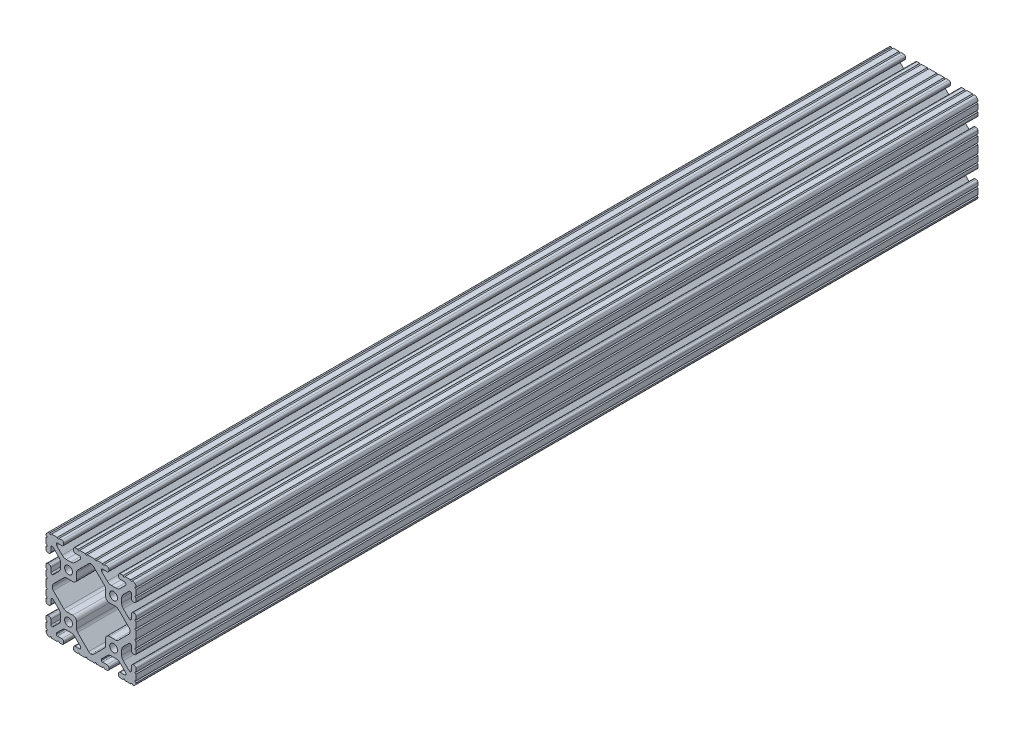
SolidWorks part; units mm, degrees
ref_plane "Front Plane" through (0, 0, 0) normal (0, 0, 1) x (1, 0, 0)
ref_plane "Top Plane" through (0, 0, 0) normal (0, 1, 0) x (1, 0, 0)
ref_plane "Right Plane" through (0, 0, 0) normal (1, 0, 0) x (0, 0, -1)
sketch "Sketch1" plane through (0, 0, 0) normal (0, 0, 1) x (1, 0, 0)
  line L0 (0, 38.1) -> (0, -38.1) construction
  line L1 (-38.1, -38.1) -> (38.1, -38.1) construction
  line L2 (-38.1, -38.1) -> (-38.1, 38.1) construction
  line L3 (-38.1, 38.1) -> (38.1, 38.1) construction
  line L4 (38.1, -38.1) -> (38.1, 38.1) construction
  line L5 (0, 38.1) -> (0, -38.1) construction
  line L6 (-38.1, 0) -> (38.1, 0) construction
  line L7 (-19.05, 19.05) -> (19.05, 19.05) construction
  line L8 (-19.05, 19.05) -> (-19.05, -19.05) construction
  line L9 (-19.05, -19.05) -> (19.05, -19.05) construction
  line L10 (19.05, 19.05) -> (19.05, -19.05) construction
  line L11 (-23.114, 38.1) -> (-23.114, -38.1) construction
  line L12 (-23.114, -38.1) -> (-14.986, 38.1) construction
  line L13 (-14.986, 38.1) -> (-14.986, -38.1) construction
  circle A0 centre (19.05, 19.05) radius 3.3274
  point P0 (0, 0)
  point P9 (0, 0)
  point P12 (-19.05, 0)
  line B0 (-11.3637, -22.8433) -> (-2.0515, -32.1555)
  line B1 (-12.2936, -15.4686) -> (-12.2936, -20.5983)
  line B2 (-20.769, -12.2936) -> (-15.4686, -12.2936)
  line B3 (-31.9021, -2.4756) -> (-23.0141, -11.3637)
  line B4 (-23.0141, 11.3637) -> (-31.9021, 2.4756)
  line B5 (-15.4686, 12.2936) -> (-20.769, 12.2936)
  line B6 (-12.2936, 20.5983) -> (-12.2936, 15.4686)
  line B7 (-2.0515, 32.1555) -> (-11.3637, 22.8433)
  line B8 (11.3637, 22.8433) -> (2.0515, 32.1555)
  line B9 (12.2936, 15.4686) -> (12.2936, 20.5983)
  line B10 (20.769, 12.2936) -> (15.4686, 12.2936)
  line B11 (31.9021, 2.4756) -> (23.0141, 11.3637)
  line B12 (23.0141, -11.3637) -> (31.9021, -2.4756)
  line B13 (15.4686, -12.2936) -> (20.769, -12.2936)
  line B14 (12.2936, -20.5983) -> (12.2936, -15.4686)
  line B15 (2.0515, -32.1555) -> (11.3637, -22.8433)
  line B16 (-4.7773, 38.1) -> (-9.6053, 38.1)
  line B17 (-11.1289, 38.1) -> (-13.4112, 38.1)
  line B18 (-14.986, 36.5252) -> (-14.986, 35.6108)
  line B19 (-13.4112, 34.036) -> (-9.652, 34.036)
  line B20 (-8.763, 33.147) -> (-8.763, 32.4935)
  line B21 (-9.0234, 31.8649) -> (-13.6907, 27.1976)
  line B22 (-17.0493, 25.8064) -> (-21.0507, 25.8064)
  line B23 (-24.4093, 27.1976) -> (-29.1002, 31.8885)
  line B24 (-29.337, 32.7207) -> (-29.337, 33.147)
  line B25 (-28.448, 34.036) -> (-24.6888, 34.036)
  line B26 (-23.114, 35.6108) -> (-23.114, 36.5252)
  line B27 (-24.6888, 38.1) -> (-27.0772, 38.1)
  line B28 (-28.6011, 38.1) -> (-33.4288, 38.1)
  line B29 (-38.1, 33.373) -> (-38.1, 28.5453)
  line B30 (-38.1, 27.0238) -> (-38.1, 24.6302)
  line B31 (-36.5252, 23.0554) -> (-35.6108, 23.0554)
  line B32 (-34.036, 24.6302) -> (-34.036, 28.448)
  line B33 (-33.147, 29.337) -> (-32.6643, 29.337)
  line B34 (-32.0357, 29.0766) -> (-27.1976, 24.2385)
  line B35 (-25.8064, 20.8799) -> (-25.8064, 17.2201)
  line B36 (-27.1976, 13.8615) -> (-31.9489, 9.1101)
  line B37 (-32.7869, 8.763) -> (-33.0603, 8.763)
  line B38 (-34.036, 9.7387) -> (-34.036, 13.4698)
  line B39 (-35.6108, 15.0446) -> (-36.5252, 15.0446)
  line B40 (-38.1, 13.4698) -> (-38.1, 11.075)
  line B41 (-38.1, 9.552) -> (-38.1, 4.7238)
  line B42 (-38.1, 3.2007) -> (-38.1, -3.2007)
  line B43 (-38.1, -4.7238) -> (-38.1, -9.552)
  line B44 (-38.1, -11.075) -> (-38.1, -13.4698)
  line B45 (-36.5252, -15.0446) -> (-35.6108, -15.0446)
  line B46 (-34.036, -13.4698) -> (-34.036, -9.7387)
  line B47 (-33.0603, -8.763) -> (-32.7869, -8.763)
  line B48 (-31.9489, -9.1101) -> (-27.1976, -13.8615)
  line B49 (-25.8064, -17.2201) -> (-25.8064, -20.8799)
  line B50 (-27.1976, -24.2385) -> (-32.0357, -29.0766)
  line B51 (-32.6643, -29.337) -> (-33.147, -29.337)
  line B52 (-34.036, -28.448) -> (-34.036, -24.6302)
  line B53 (-35.6108, -23.0554) -> (-36.5252, -23.0554)
  line B54 (-38.1, -24.6302) -> (-38.1, -27.0238)
  line B55 (-38.1, -28.5453) -> (-38.1, -33.373)
  line B56 (-33.4288, -38.1) -> (-28.6011, -38.1)
  line B57 (-27.0772, -38.1) -> (-24.6888, -38.1)
  line B58 (-23.114, -36.5252) -> (-23.114, -35.6108)
  line B59 (-24.6888, -34.036) -> (-28.448, -34.036)
  line B60 (-29.337, -33.147) -> (-29.337, -32.7207)
  line B61 (-29.1002, -31.8885) -> (-24.4093, -27.1976)
  line B62 (-21.0507, -25.8064) -> (-17.0493, -25.8064)
  line B63 (-13.6907, -27.1976) -> (-9.0234, -31.8649)
  line B64 (-8.763, -32.4935) -> (-8.763, -33.147)
  line B65 (-9.652, -34.036) -> (-13.4112, -34.036)
  line B66 (-14.986, -35.6108) -> (-14.986, -36.5252)
  line B67 (-13.4112, -38.1) -> (-11.1289, -38.1)
  line B68 (-9.6053, -38.1) -> (-4.7773, -38.1)
  line B69 (-3.2537, -38.1) -> (3.2537, -38.1)
  line B70 (4.7773, -38.1) -> (9.6053, -38.1)
  line B71 (11.1289, -38.1) -> (13.4112, -38.1)
  line B72 (14.986, -36.5252) -> (14.986, -35.6108)
  line B73 (13.4112, -34.036) -> (9.652, -34.036)
  line B74 (8.763, -33.147) -> (8.763, -32.4935)
  line B75 (9.0234, -31.8649) -> (13.6907, -27.1976)
  line B76 (17.0493, -25.8064) -> (21.0507, -25.8064)
  line B77 (24.4093, -27.1976) -> (29.1002, -31.8885)
  line B78 (29.337, -32.7207) -> (29.337, -33.147)
  line B79 (28.448, -34.036) -> (24.6888, -34.036)
  line B80 (23.114, -35.6108) -> (23.114, -36.5252)
  line B81 (24.6888, -38.1) -> (27.0772, -38.1)
  line B82 (28.6011, -38.1) -> (33.4288, -38.1)
  line B83 (38.1, -33.373) -> (38.1, -28.5453)
  line B84 (38.1, -27.0238) -> (38.1, -24.6302)
  line B85 (36.5252, -23.0554) -> (35.6108, -23.0554)
  line B86 (34.036, -24.6302) -> (34.036, -28.448)
  line B87 (33.147, -29.337) -> (32.6643, -29.337)
  line B88 (32.0357, -29.0766) -> (27.1976, -24.2385)
  line B89 (25.8064, -20.8799) -> (25.8064, -17.2201)
  line B90 (27.1976, -13.8615) -> (31.9489, -9.1101)
  line B91 (32.7869, -8.763) -> (33.0603, -8.763)
  line B92 (34.036, -9.7387) -> (34.036, -13.4698)
  line B93 (35.6108, -15.0446) -> (36.5252, -15.0446)
  line B94 (38.1, -13.4698) -> (38.1, -11.075)
  line B95 (38.1, -9.552) -> (38.1, -4.7238)
  line B96 (38.1, -3.2007) -> (38.1, 3.2007)
  line B97 (38.1, 4.7238) -> (38.1, 9.552)
  line B98 (38.1, 11.075) -> (38.1, 13.4698)
  line B99 (36.5252, 15.0446) -> (35.6108, 15.0446)
  line B100 (34.036, 13.4698) -> (34.036, 9.7387)
  line B101 (33.0603, 8.763) -> (32.7869, 8.763)
  line B102 (31.9489, 9.1101) -> (27.1976, 13.8615)
  line B103 (25.8064, 17.2201) -> (25.8064, 20.8799)
  line B104 (27.1976, 24.2385) -> (32.0357, 29.0766)
  line B105 (32.6643, 29.337) -> (33.147, 29.337)
  line B106 (34.036, 28.448) -> (34.036, 24.6302)
  line B107 (35.6108, 23.0554) -> (36.5252, 23.0554)
  line B108 (38.1, 24.6302) -> (38.1, 27.0238)
  line B109 (38.1, 28.5453) -> (38.1, 33.373)
  line B110 (33.4288, 38.1) -> (28.6011, 38.1)
  line B111 (27.0772, 38.1) -> (24.6888, 38.1)
  line B112 (23.114, 36.5252) -> (23.114, 35.6108)
  line B113 (24.6888, 34.036) -> (28.448, 34.036)
  line B114 (29.337, 33.147) -> (29.337, 32.7207)
  line B115 (29.1002, 31.8885) -> (24.4093, 27.1976)
  line B116 (21.0507, 25.8064) -> (17.0493, 25.8064)
  line B117 (13.6907, 27.1976) -> (9.0234, 31.8649)
  line B118 (8.763, 32.4935) -> (8.763, 33.147)
  line B119 (9.652, 34.036) -> (13.4112, 34.036)
  line B120 (14.986, 35.6108) -> (14.986, 36.5252)
  line B121 (13.4112, 38.1) -> (11.1289, 38.1)
  line B122 (9.6053, 38.1) -> (4.7773, 38.1)
  line B123 (3.2537, 38.1) -> (-3.2537, 38.1)
  circle B124 centre (-19.05, 19.05) radius 3.3274
  circle B125 centre (-19.05, -19.05) radius 3.3274
  circle B126 centre (19.05, -19.05) radius 3.3274
  circle B127 centre (19.05, 19.05) radius 3.3274
  arc B128 (0, -33.011) -> (2.0515, -32.1555) centre (-0.0139, -30.09) ccw
  arc B129 (-2.0515, -32.1555) -> (0, -33.011) centre (0.0139, -30.09) ccw
  arc B130 (-12.2936, -20.5983) -> (-11.3637, -22.8433) centre (-9.1186, -20.5983) ccw
  arc B131 (-12.2936, -15.4686) -> (-15.4686, -12.2936) centre (-15.4686, -15.4686) ccw
  arc B132 (-23.0141, -11.3637) -> (-20.769, -12.2936) centre (-20.769, -9.1186) ccw
  arc B133 (-32.7287, 0) -> (-31.9021, -2.4756) centre (-29.8367, -0.4102) ccw
  arc B134 (-31.9021, 2.4756) -> (-32.7287, 0) centre (-29.8367, 0.4102) ccw
  arc B135 (-20.769, 12.2936) -> (-23.0141, 11.3637) centre (-20.769, 9.1186) ccw
  arc B136 (-15.4686, 12.2936) -> (-12.2936, 15.4686) centre (-15.4686, 15.4686) ccw
  arc B137 (-11.3637, 22.8433) -> (-12.2936, 20.5983) centre (-9.1186, 20.5983) ccw
  arc B138 (0, 33.011) -> (-2.0515, 32.1555) centre (0.0139, 30.09) ccw
  arc B139 (2.0515, 32.1555) -> (0, 33.011) centre (-0.0139, 30.09) ccw
  arc B140 (12.2936, 20.5983) -> (11.3637, 22.8433) centre (9.1186, 20.5983) ccw
  arc B141 (12.2936, 15.4686) -> (15.4686, 12.2936) centre (15.4686, 15.4686) ccw
  arc B142 (23.0141, 11.3637) -> (20.769, 12.2936) centre (20.769, 9.1186) ccw
  arc B143 (32.7287, 0) -> (31.9021, 2.4756) centre (29.8367, 0.4102) ccw
  arc B144 (31.9021, -2.4756) -> (32.7287, 0) centre (29.8367, -0.4102) ccw
  arc B145 (20.769, -12.2936) -> (23.0141, -11.3637) centre (20.769, -9.1186) ccw
  arc B146 (15.4686, -12.2936) -> (12.2936, -15.4686) centre (15.4686, -15.4686) ccw
  arc B147 (11.3637, -22.8433) -> (12.2936, -20.5983) centre (9.1186, -20.5983) ccw
  arc B148 (-4.7773, 38.1) -> (-3.2537, 38.1) centre (-4.0155, 38.0824) ccw
  arc B149 (-11.1289, 38.1) -> (-9.6053, 38.1) centre (-10.3671, 38.0824) ccw
  arc B150 (-13.4112, 38.1) -> (-14.986, 36.5252) centre (-13.4112, 36.5252) ccw
  arc B151 (-14.986, 35.6108) -> (-13.4112, 34.036) centre (-13.4112, 35.6108) ccw
  arc B152 (-8.763, 33.147) -> (-9.652, 34.036) centre (-9.652, 33.147) ccw
  arc B153 (-9.0234, 31.8649) -> (-8.763, 32.4935) centre (-9.652, 32.4935) ccw
  arc B154 (-17.0493, 25.8064) -> (-13.6907, 27.1976) centre (-17.0493, 30.5562) ccw
  arc B155 (-24.4093, 27.1976) -> (-21.0507, 25.8064) centre (-21.0507, 30.5562) ccw
  arc B156 (-29.337, 32.7207) -> (-29.1002, 31.8885) centre (-28.4716, 32.5172) ccw
  arc B157 (-28.448, 34.036) -> (-29.337, 33.147) centre (-28.448, 33.147) ccw
  arc B158 (-24.6888, 34.036) -> (-23.114, 35.6108) centre (-24.6888, 35.6108) ccw
  arc B159 (-23.114, 36.5252) -> (-24.6888, 38.1) centre (-24.6888, 36.5252) ccw
  arc B160 (-28.6011, 38.1) -> (-27.0772, 38.1) centre (-27.8392, 38.0824) ccw
  arc B161 (-34.9527, 38.1) -> (-33.4288, 38.1) centre (-34.1907, 38.0824) ccw
  arc B162 (-34.9527, 38.1) -> (-37.0861, 37.1826) centre (-34.8521, 34.9266) ccw
  arc B163 (-37.0861, 37.1826) -> (-38.1, 34.8455) centre (-34.925, 34.8566) ccw
  arc B164 (-38.1, 33.373) -> (-38.1, 34.8455) centre (-37.9035, 34.1092) ccw
  arc B165 (-38.1, 27.0238) -> (-38.1, 28.5453) centre (-37.9035, 27.7845) ccw
  arc B166 (-38.1, 24.6302) -> (-36.5252, 23.0554) centre (-36.5252, 24.6302) ccw
  arc B167 (-35.6108, 23.0554) -> (-34.036, 24.6302) centre (-35.6108, 24.6302) ccw
  arc B168 (-33.147, 29.337) -> (-34.036, 28.448) centre (-33.147, 28.448) ccw
  arc B169 (-32.0357, 29.0766) -> (-32.6643, 29.337) centre (-32.6643, 28.448) ccw
  arc B170 (-25.8064, 20.8799) -> (-27.1976, 24.2385) centre (-30.5562, 20.8799) ccw
  arc B171 (-27.1976, 13.8615) -> (-25.8064, 17.2201) centre (-30.5562, 17.2201) ccw
  arc B172 (-32.7869, 8.763) -> (-31.9489, 9.1101) centre (-32.7869, 9.9481) ccw
  arc B173 (-34.036, 9.7387) -> (-33.0603, 8.763) centre (-33.0603, 9.7387) ccw
  arc B174 (-34.036, 13.4698) -> (-35.6108, 15.0446) centre (-35.6108, 13.4698) ccw
  arc B175 (-36.5252, 15.0446) -> (-38.1, 13.4698) centre (-36.5252, 13.4698) ccw
  arc B176 (-38.1, 9.552) -> (-38.1, 11.075) centre (-37.9035, 10.3135) ccw
  arc B177 (-38.1, 3.2007) -> (-38.1, 4.7238) centre (-37.9035, 3.9622) ccw
  arc B178 (-38.1, -4.7238) -> (-38.1, -3.2007) centre (-37.9035, -3.9622) ccw
  arc B179 (-38.1, -11.075) -> (-38.1, -9.552) centre (-37.9035, -10.3135) ccw
  arc B180 (-38.1, -13.4698) -> (-36.5252, -15.0446) centre (-36.5252, -13.4698) ccw
  arc B181 (-35.6108, -15.0446) -> (-34.036, -13.4698) centre (-35.6108, -13.4698) ccw
  arc B182 (-33.0603, -8.763) -> (-34.036, -9.7387) centre (-33.0603, -9.7387) ccw
  arc B183 (-31.9489, -9.1101) -> (-32.7869, -8.763) centre (-32.7869, -9.9481) ccw
  arc B184 (-25.8064, -17.2201) -> (-27.1976, -13.8615) centre (-30.5562, -17.2201) ccw
  arc B185 (-27.1976, -24.2385) -> (-25.8064, -20.8799) centre (-30.5562, -20.8799) ccw
  arc B186 (-32.6643, -29.337) -> (-32.0357, -29.0766) centre (-32.6643, -28.448) ccw
  arc B187 (-34.036, -28.448) -> (-33.147, -29.337) centre (-33.147, -28.448) ccw
  arc B188 (-34.036, -24.6302) -> (-35.6108, -23.0554) centre (-35.6108, -24.6302) ccw
  arc B189 (-36.5252, -23.0554) -> (-38.1, -24.6302) centre (-36.5252, -24.6302) ccw
  arc B190 (-38.1, -28.5453) -> (-38.1, -27.0238) centre (-37.9035, -27.7845) ccw
  arc B191 (-38.1, -34.8455) -> (-38.1, -33.373) centre (-37.9035, -34.1092) ccw
  arc B192 (-38.1, -34.8455) -> (-37.0861, -37.1826) centre (-34.925, -34.8566) ccw
  arc B193 (-37.0861, -37.1826) -> (-34.9527, -38.1) centre (-34.8521, -34.9266) ccw
  arc B194 (-33.4288, -38.1) -> (-34.9527, -38.1) centre (-34.1907, -38.0824) ccw
  arc B195 (-27.0772, -38.1) -> (-28.6011, -38.1) centre (-27.8392, -38.0824) ccw
  arc B196 (-24.6888, -38.1) -> (-23.114, -36.5252) centre (-24.6888, -36.5252) ccw
  arc B197 (-23.114, -35.6108) -> (-24.6888, -34.036) centre (-24.6888, -35.6108) ccw
  arc B198 (-29.337, -33.147) -> (-28.448, -34.036) centre (-28.448, -33.147) ccw
  arc B199 (-29.1002, -31.8885) -> (-29.337, -32.7207) centre (-28.4716, -32.5172) ccw
  arc B200 (-21.0507, -25.8064) -> (-24.4093, -27.1976) centre (-21.0507, -30.5562) ccw
  arc B201 (-13.6907, -27.1976) -> (-17.0493, -25.8064) centre (-17.0493, -30.5562) ccw
  arc B202 (-8.763, -32.4935) -> (-9.0234, -31.8649) centre (-9.652, -32.4935) ccw
  arc B203 (-9.652, -34.036) -> (-8.763, -33.147) centre (-9.652, -33.147) ccw
  arc B204 (-13.4112, -34.036) -> (-14.986, -35.6108) centre (-13.4112, -35.6108) ccw
  arc B205 (-14.986, -36.5252) -> (-13.4112, -38.1) centre (-13.4112, -36.5252) ccw
  arc B206 (-9.6053, -38.1) -> (-11.1289, -38.1) centre (-10.3671, -38.0824) ccw
  arc B207 (-3.2537, -38.1) -> (-4.7773, -38.1) centre (-4.0155, -38.0824) ccw
  arc B208 (4.7773, -38.1) -> (3.2537, -38.1) centre (4.0155, -38.0824) ccw
  arc B209 (11.1289, -38.1) -> (9.6053, -38.1) centre (10.3671, -38.0824) ccw
  arc B210 (13.4112, -38.1) -> (14.986, -36.5252) centre (13.4112, -36.5252) ccw
  arc B211 (14.986, -35.6108) -> (13.4112, -34.036) centre (13.4112, -35.6108) ccw
  arc B212 (8.763, -33.147) -> (9.652, -34.036) centre (9.652, -33.147) ccw
  arc B213 (9.0234, -31.8649) -> (8.763, -32.4935) centre (9.652, -32.4935) ccw
  arc B214 (17.0493, -25.8064) -> (13.6907, -27.1976) centre (17.0493, -30.5562) ccw
  arc B215 (24.4093, -27.1976) -> (21.0507, -25.8064) centre (21.0507, -30.5562) ccw
  arc B216 (29.337, -32.7207) -> (29.1002, -31.8885) centre (28.4716, -32.5172) ccw
  arc B217 (28.448, -34.036) -> (29.337, -33.147) centre (28.448, -33.147) ccw
  arc B218 (24.6888, -34.036) -> (23.114, -35.6108) centre (24.6888, -35.6108) ccw
  arc B219 (23.114, -36.5252) -> (24.6888, -38.1) centre (24.6888, -36.5252) ccw
  arc B220 (28.6011, -38.1) -> (27.0772, -38.1) centre (27.8392, -38.0824) ccw
  arc B221 (34.9527, -38.1) -> (33.4288, -38.1) centre (34.1907, -38.0824) ccw
  arc B222 (34.9527, -38.1) -> (37.0861, -37.1826) centre (34.8521, -34.9266) ccw
  arc B223 (37.0861, -37.1826) -> (38.1, -34.8455) centre (34.925, -34.8566) ccw
  arc B224 (38.1, -33.373) -> (38.1, -34.8455) centre (37.9035, -34.1092) ccw
  arc B225 (38.1, -27.0238) -> (38.1, -28.5453) centre (37.9035, -27.7845) ccw
  arc B226 (38.1, -24.6302) -> (36.5252, -23.0554) centre (36.5252, -24.6302) ccw
  arc B227 (35.6108, -23.0554) -> (34.036, -24.6302) centre (35.6108, -24.6302) ccw
  arc B228 (33.147, -29.337) -> (34.036, -28.448) centre (33.147, -28.448) ccw
  arc B229 (32.0357, -29.0766) -> (32.6643, -29.337) centre (32.6643, -28.448) ccw
  arc B230 (25.8064, -20.8799) -> (27.1976, -24.2385) centre (30.5562, -20.8799) ccw
  arc B231 (27.1976, -13.8615) -> (25.8064, -17.2201) centre (30.5562, -17.2201) ccw
  arc B232 (32.7869, -8.763) -> (31.9489, -9.1101) centre (32.7869, -9.9481) ccw
  arc B233 (34.036, -9.7387) -> (33.0603, -8.763) centre (33.0603, -9.7387) ccw
  arc B234 (34.036, -13.4698) -> (35.6108, -15.0446) centre (35.6108, -13.4698) ccw
  arc B235 (36.5252, -15.0446) -> (38.1, -13.4698) centre (36.5252, -13.4698) ccw
  arc B236 (38.1, -9.552) -> (38.1, -11.075) centre (37.9035, -10.3135) ccw
  arc B237 (38.1, -3.2007) -> (38.1, -4.7238) centre (37.9035, -3.9622) ccw
  arc B238 (38.1, 4.7238) -> (38.1, 3.2007) centre (37.9035, 3.9622) ccw
  arc B239 (38.1, 11.075) -> (38.1, 9.552) centre (37.9035, 10.3135) ccw
  arc B240 (38.1, 13.4698) -> (36.5252, 15.0446) centre (36.5252, 13.4698) ccw
  arc B241 (35.6108, 15.0446) -> (34.036, 13.4698) centre (35.6108, 13.4698) ccw
  arc B242 (33.0603, 8.763) -> (34.036, 9.7387) centre (33.0603, 9.7387) ccw
  arc B243 (31.9489, 9.1101) -> (32.7869, 8.763) centre (32.7869, 9.9481) ccw
  arc B244 (25.8064, 17.2201) -> (27.1976, 13.8615) centre (30.5562, 17.2201) ccw
  arc B245 (27.1976, 24.2385) -> (25.8064, 20.8799) centre (30.5562, 20.8799) ccw
  arc B246 (32.6643, 29.337) -> (32.0357, 29.0766) centre (32.6643, 28.448) ccw
  arc B247 (34.036, 28.448) -> (33.147, 29.337) centre (33.147, 28.448) ccw
  arc B248 (34.036, 24.6302) -> (35.6108, 23.0554) centre (35.6108, 24.6302) ccw
  arc B249 (36.5252, 23.0554) -> (38.1, 24.6302) centre (36.5252, 24.6302) ccw
  arc B250 (38.1, 28.5453) -> (38.1, 27.0238) centre (37.9035, 27.7845) ccw
  arc B251 (38.1, 34.8455) -> (38.1, 33.373) centre (37.9035, 34.1092) ccw
  arc B252 (38.1, 34.8455) -> (37.0861, 37.1826) centre (34.925, 34.8566) ccw
  arc B253 (37.0861, 37.1826) -> (34.9527, 38.1) centre (34.8521, 34.9266) ccw
  arc B254 (33.4288, 38.1) -> (34.9527, 38.1) centre (34.1907, 38.0824) ccw
  arc B255 (27.0772, 38.1) -> (28.6011, 38.1) centre (27.8392, 38.0824) ccw
  arc B256 (24.6888, 38.1) -> (23.114, 36.5252) centre (24.6888, 36.5252) ccw
  arc B257 (23.114, 35.6108) -> (24.6888, 34.036) centre (24.6888, 35.6108) ccw
  arc B258 (29.337, 33.147) -> (28.448, 34.036) centre (28.448, 33.147) ccw
  arc B259 (29.1002, 31.8885) -> (29.337, 32.7207) centre (28.4716, 32.5172) ccw
  arc B260 (21.0507, 25.8064) -> (24.4093, 27.1976) centre (21.0507, 30.5562) ccw
  arc B261 (13.6907, 27.1976) -> (17.0493, 25.8064) centre (17.0493, 30.5562) ccw
  arc B262 (8.763, 32.4935) -> (9.0234, 31.8649) centre (9.652, 32.4935) ccw
  arc B263 (9.652, 34.036) -> (8.763, 33.147) centre (9.652, 33.147) ccw
  arc B264 (13.4112, 34.036) -> (14.986, 35.6108) centre (13.4112, 35.6108) ccw
  arc B265 (14.986, 36.5252) -> (13.4112, 38.1) centre (13.4112, 36.5252) ccw
  arc B266 (9.6053, 38.1) -> (11.1289, 38.1) centre (10.3671, 38.0824) ccw
  arc B267 (3.2537, 38.1) -> (4.7773, 38.1) centre (4.0155, 38.0824) ccw
  dimension "Center Hole Diameter" = 6.6548
  dimension "Rail Width" = 76.2
  dimension "Rail Height" = 76.2
  dimension "T-Slot Width" = 8.128
sketch_block_instance "Block1-1"
sketch_block "Block1"
sketch "Sketch2" plane through (0, 0, 0) normal (1, 0, 0) x (0, 0, -1)
  line L0 (-355.6, 0) -> (355.6, 0) construction
  line L1 (-355.6, 38.1) -> (-355.6, -38.1) construction
  line L2 (-355.6, -38.1) -> (355.6, -38.1) construction
  line L3 (355.6, -38.1) -> (355.6, 38.1) construction
  line L4 (-254, 0) -> (-254, 38.1) construction
  line L5 (-254, 38.1) -> (254, 38.1) construction
  line L6 (254, 38.1) -> (254, 0) construction
  point P5 (254, 0)
  point P10 (-254, 0)
  dimension "D1" = 101.6
  dimension "Length" = 711.2
  dimension "D2" = 101.6
sketch "Sketch3" plane through (0, 0, 0) normal (0, 0, 1) x (1, 0, 0)
  line L0 (-11.3637, -22.8433) -> (-2.0515, -32.1555) construction
  line L1 (-12.2936, -15.4686) -> (-12.2936, -20.5983) construction
  line L2 (-20.769, -12.2936) -> (-15.4686, -12.2936) construction
  line L3 (-31.9021, -2.4756) -> (-23.0141, -11.3637) construction
  line L4 (-23.0141, 11.3637) -> (-31.9021, 2.4756) construction
  line L5 (-15.4686, 12.2936) -> (-20.769, 12.2936) construction
  line L6 (-12.2936, 20.5983) -> (-12.2936, 15.4686) construction
  line L7 (-2.0515, 32.1555) -> (-11.3637, 22.8433) construction
  line L8 (11.3637, 22.8433) -> (2.0515, 32.1555) construction
  line L9 (12.2936, 15.4686) -> (12.2936, 20.5983) construction
  line L10 (20.769, 12.2936) -> (15.4686, 12.2936) construction
  line L11 (31.9021, 2.4756) -> (23.0141, 11.3637) construction
  line L12 (23.0141, -11.3637) -> (31.9021, -2.4756) construction
  line L13 (15.4686, -12.2936) -> (20.769, -12.2936) construction
  line L14 (12.2936, -20.5983) -> (12.2936, -15.4686) construction
  line L15 (2.0515, -32.1555) -> (11.3637, -22.8433) construction
  line L16 (34.036, 28.448) -> (34.036, 24.6302) construction
  line L17 (35.6108, 23.0554) -> (36.5252, 23.0554) construction
  line L18 (38.1, 24.6302) -> (38.1, 27.0238) construction
  line L19 (38.1, 28.5453) -> (38.1, 33.373) construction
  line L20 (33.4288, 38.1) -> (28.6011, 38.1) construction
  line L21 (27.0772, 38.1) -> (24.6888, 38.1) construction
  line L22 (23.114, 36.5252) -> (23.114, 35.6108) construction
  line L23 (24.6888, 34.036) -> (28.448, 34.036) construction
  line L24 (29.337, 33.147) -> (29.337, 32.7207) construction
  line L25 (29.1002, 31.8885) -> (24.4093, 27.1976) construction
  line L26 (21.0507, 25.8064) -> (17.0493, 25.8064) construction
  line L27 (13.6907, 27.1976) -> (9.0234, 31.8649) construction
  line L28 (8.763, 32.4935) -> (8.763, 33.147) construction
  line L29 (9.652, 34.036) -> (13.4112, 34.036) construction
  line L30 (14.986, 35.6108) -> (14.986, 36.5252) construction
  line L31 (13.4112, 38.1) -> (11.1289, 38.1) construction
  line L32 (9.6053, 38.1) -> (4.7773, 38.1) construction
  line L33 (3.2537, 38.1) -> (-3.2537, 38.1) construction
  line L34 (-4.7773, 38.1) -> (-9.6053, 38.1) construction
  line L35 (-11.1289, 38.1) -> (-13.4112, 38.1) construction
  line L36 (-14.986, 36.5252) -> (-14.986, 35.6108) construction
  line L37 (-13.4112, 34.036) -> (-9.652, 34.036) construction
  line L38 (-8.763, 33.147) -> (-8.763, 32.4935) construction
  line L39 (-9.0234, 31.8649) -> (-13.6907, 27.1976) construction
  line L40 (-17.0493, 25.8064) -> (-21.0507, 25.8064) construction
  line L41 (-24.4093, 27.1976) -> (-29.1002, 31.8885) construction
  line L42 (-29.337, 32.7207) -> (-29.337, 33.147) construction
  line L43 (-28.448, 34.036) -> (-24.6888, 34.036) construction
  line L44 (-23.114, 35.6108) -> (-23.114, 36.5252) construction
  line L45 (-24.6888, 38.1) -> (-27.0772, 38.1) construction
  line L46 (-28.6011, 38.1) -> (-33.4288, 38.1) construction
  line L47 (-38.1, 33.373) -> (-38.1, 28.5453) construction
  line L48 (-38.1, 27.0238) -> (-38.1, 24.6302) construction
  line L49 (-36.5252, 23.0554) -> (-35.6108, 23.0554) construction
  line L50 (-34.036, 24.6302) -> (-34.036, 28.448) construction
  line L51 (-33.147, 29.337) -> (-32.6643, 29.337) construction
  line L52 (-32.0357, 29.0766) -> (-27.1976, 24.2385) construction
  line L53 (-25.8064, 20.8799) -> (-25.8064, 17.2201) construction
  line L54 (-27.1976, 13.8615) -> (-31.9489, 9.1101) construction
  line L55 (-32.7869, 8.763) -> (-33.0603, 8.763) construction
  line L56 (-34.036, 9.7387) -> (-34.036, 13.4698) construction
  line L57 (-35.6108, 15.0446) -> (-36.5252, 15.0446) construction
  line L58 (-38.1, 13.4698) -> (-38.1, 11.075) construction
  line L59 (-38.1, 9.552) -> (-38.1, 4.7238) construction
  line L60 (-38.1, 3.2007) -> (-38.1, -3.2007) construction
  line L61 (-38.1, -4.7238) -> (-38.1, -9.552) construction
  line L62 (-38.1, -11.075) -> (-38.1, -13.4698) construction
  line L63 (-36.5252, -15.0446) -> (-35.6108, -15.0446) construction
  line L64 (-34.036, -13.4698) -> (-34.036, -9.7387) construction
  line L65 (-33.0603, -8.763) -> (-32.7869, -8.763) construction
  line L66 (-31.9489, -9.1101) -> (-27.1976, -13.8615) construction
  line L67 (-25.8064, -17.2201) -> (-25.8064, -20.8799) construction
  line L68 (-27.1976, -24.2385) -> (-32.0357, -29.0766) construction
  line L69 (-32.6643, -29.337) -> (-33.147, -29.337) construction
  line L70 (-34.036, -28.448) -> (-34.036, -24.6302) construction
  line L71 (-35.6108, -23.0554) -> (-36.5252, -23.0554) construction
  line L72 (-38.1, -24.6302) -> (-38.1, -27.0238) construction
  line L73 (-38.1, -28.5453) -> (-38.1, -33.373) construction
  line L74 (-33.4288, -38.1) -> (-28.6011, -38.1) construction
  line L75 (-27.0772, -38.1) -> (-24.6888, -38.1) construction
  line L76 (-23.114, -36.5252) -> (-23.114, -35.6108) construction
  line L77 (-24.6888, -34.036) -> (-28.448, -34.036) construction
  line L78 (-29.337, -33.147) -> (-29.337, -32.7207) construction
  line L79 (-29.1002, -31.8885) -> (-24.4093, -27.1976) construction
  line L80 (-21.0507, -25.8064) -> (-17.0493, -25.8064) construction
  line L81 (-13.6907, -27.1976) -> (-9.0234, -31.8649) construction
  line L82 (-8.763, -32.4935) -> (-8.763, -33.147) construction
  line L83 (-9.652, -34.036) -> (-13.4112, -34.036) construction
  line L84 (-14.986, -35.6108) -> (-14.986, -36.5252) construction
  line L85 (-13.4112, -38.1) -> (-11.1289, -38.1) construction
  line L86 (-9.6053, -38.1) -> (-4.7773, -38.1) construction
  line L87 (-3.2537, -38.1) -> (3.2537, -38.1) construction
  line L88 (4.7773, -38.1) -> (9.6053, -38.1) construction
  line L89 (11.1289, -38.1) -> (13.4112, -38.1) construction
  line L90 (14.986, -36.5252) -> (14.986, -35.6108) construction
  line L91 (13.4112, -34.036) -> (9.652, -34.036) construction
  line L92 (8.763, -33.147) -> (8.763, -32.4935) construction
  line L93 (9.0234, -31.8649) -> (13.6907, -27.1976) construction
  line L94 (17.0493, -25.8064) -> (21.0507, -25.8064) construction
  line L95 (24.4093, -27.1976) -> (29.1002, -31.8885) construction
  line L96 (29.337, -32.7207) -> (29.337, -33.147) construction
  line L97 (28.448, -34.036) -> (24.6888, -34.036) construction
  line L98 (23.114, -35.6108) -> (23.114, -36.5252) construction
  line L99 (24.6888, -38.1) -> (27.0772, -38.1) construction
  line L100 (28.6011, -38.1) -> (33.4288, -38.1) construction
  line L101 (38.1, -33.373) -> (38.1, -28.5453) construction
  line L102 (38.1, -27.0238) -> (38.1, -24.6302) construction
  line L103 (36.5252, -23.0554) -> (35.6108, -23.0554) construction
  line L104 (34.036, -24.6302) -> (34.036, -28.448) construction
  line L105 (33.147, -29.337) -> (32.6643, -29.337) construction
  line L106 (32.0357, -29.0766) -> (27.1976, -24.2385) construction
  line L107 (25.8064, -20.8799) -> (25.8064, -17.2201) construction
  line L108 (27.1976, -13.8615) -> (31.9489, -9.1101) construction
  line L109 (32.7869, -8.763) -> (33.0603, -8.763) construction
  line L110 (34.036, -9.7387) -> (34.036, -13.4698) construction
  line L111 (35.6108, -15.0446) -> (36.5252, -15.0446) construction
  line L112 (38.1, -13.4698) -> (38.1, -11.075) construction
  line L113 (38.1, -9.552) -> (38.1, -4.7238) construction
  line L114 (38.1, -3.2007) -> (38.1, 3.2007) construction
  line L115 (38.1, 4.7238) -> (38.1, 9.552) construction
  line L116 (38.1, 11.075) -> (38.1, 13.4698) construction
  line L117 (36.5252, 15.0446) -> (35.6108, 15.0446) construction
  line L118 (34.036, 13.4698) -> (34.036, 9.7387) construction
  line L119 (33.0603, 8.763) -> (32.7869, 8.763) construction
  line L120 (31.9489, 9.1101) -> (27.1976, 13.8615) construction
  line L121 (25.8064, 17.2201) -> (25.8064, 20.8799) construction
  line L122 (27.1976, 24.2385) -> (32.0357, 29.0766) construction
  line L123 (32.6643, 29.337) -> (33.147, 29.337) construction
  line L124 (-11.3637, -22.8433) -> (-2.0515, -32.1555)
  line L125 (-12.2936, -15.4686) -> (-12.2936, -20.5983)
  line L126 (-20.769, -12.2936) -> (-15.4686, -12.2936)
  line L127 (-31.9021, -2.4756) -> (-23.0141, -11.3637)
  line L128 (-23.0141, 11.3637) -> (-31.9021, 2.4756)
  line L129 (-15.4686, 12.2936) -> (-20.769, 12.2936)
  line L130 (-12.2936, 20.5983) -> (-12.2936, 15.4686)
  line L131 (-2.0515, 32.1555) -> (-11.3637, 22.8433)
  line L132 (11.3637, 22.8433) -> (2.0515, 32.1555)
  line L133 (12.2936, 15.4686) -> (12.2936, 20.5983)
  line L134 (20.769, 12.2936) -> (15.4686, 12.2936)
  line L135 (31.9021, 2.4756) -> (23.0141, 11.3637)
  line L136 (23.0141, -11.3637) -> (31.9021, -2.4756)
  line L137 (15.4686, -12.2936) -> (20.769, -12.2936)
  line L138 (12.2936, -20.5983) -> (12.2936, -15.4686)
  line L139 (2.0515, -32.1555) -> (11.3637, -22.8433)
  line L140 (34.036, 28.448) -> (34.036, 24.6302)
  line L141 (35.6108, 23.0554) -> (36.5252, 23.0554)
  line L142 (38.1, 24.6302) -> (38.1, 27.0238)
  line L143 (38.1, 28.5453) -> (38.1, 33.373)
  line L144 (33.4288, 38.1) -> (28.6011, 38.1)
  line L145 (27.0772, 38.1) -> (24.6888, 38.1)
  line L146 (23.114, 36.5252) -> (23.114, 35.6108)
  line L147 (24.6888, 34.036) -> (28.448, 34.036)
  line L148 (29.337, 33.147) -> (29.337, 32.7207)
  line L149 (29.1002, 31.8885) -> (24.4093, 27.1976)
  line L150 (21.0507, 25.8064) -> (17.0493, 25.8064)
  line L151 (13.6907, 27.1976) -> (9.0234, 31.8649)
  line L152 (8.763, 32.4935) -> (8.763, 33.147)
  line L153 (9.652, 34.036) -> (13.4112, 34.036)
  line L154 (14.986, 35.6108) -> (14.986, 36.5252)
  line L155 (13.4112, 38.1) -> (11.1289, 38.1)
  line L156 (9.6053, 38.1) -> (4.7773, 38.1)
  line L157 (3.2537, 38.1) -> (-3.2537, 38.1)
  line L158 (-4.7773, 38.1) -> (-9.6053, 38.1)
  line L159 (-11.1289, 38.1) -> (-13.4112, 38.1)
  line L160 (-14.986, 36.5252) -> (-14.986, 35.6108)
  line L161 (-13.4112, 34.036) -> (-9.652, 34.036)
  line L162 (-8.763, 33.147) -> (-8.763, 32.4935)
  line L163 (-9.0234, 31.8649) -> (-13.6907, 27.1976)
  line L164 (-17.0493, 25.8064) -> (-21.0507, 25.8064)
  line L165 (-24.4093, 27.1976) -> (-29.1002, 31.8885)
  line L166 (-29.337, 32.7207) -> (-29.337, 33.147)
  line L167 (-28.448, 34.036) -> (-24.6888, 34.036)
  line L168 (-23.114, 35.6108) -> (-23.114, 36.5252)
  line L169 (-24.6888, 38.1) -> (-27.0772, 38.1)
  line L170 (-28.6011, 38.1) -> (-33.4288, 38.1)
  line L171 (-38.1, 33.373) -> (-38.1, 28.5453)
  line L172 (-38.1, 27.0238) -> (-38.1, 24.6302)
  line L173 (-36.5252, 23.0554) -> (-35.6108, 23.0554)
  line L174 (-34.036, 24.6302) -> (-34.036, 28.448)
  line L175 (-33.147, 29.337) -> (-32.6643, 29.337)
  line L176 (-32.0357, 29.0766) -> (-27.1976, 24.2385)
  line L177 (-25.8064, 20.8799) -> (-25.8064, 17.2201)
  line L178 (-27.1976, 13.8615) -> (-31.9489, 9.1101)
  line L179 (-32.7869, 8.763) -> (-33.0603, 8.763)
  line L180 (-34.036, 9.7387) -> (-34.036, 13.4698)
  line L181 (-35.6108, 15.0446) -> (-36.5252, 15.0446)
  line L182 (-38.1, 13.4698) -> (-38.1, 11.075)
  line L183 (-38.1, 9.552) -> (-38.1, 4.7238)
  line L184 (-38.1, 3.2007) -> (-38.1, -3.2007)
  line L185 (-38.1, -4.7238) -> (-38.1, -9.552)
  line L186 (-38.1, -11.075) -> (-38.1, -13.4698)
  line L187 (-36.5252, -15.0446) -> (-35.6108, -15.0446)
  line L188 (-34.036, -13.4698) -> (-34.036, -9.7387)
  line L189 (-33.0603, -8.763) -> (-32.7869, -8.763)
  line L190 (-31.9489, -9.1101) -> (-27.1976, -13.8615)
  line L191 (-25.8064, -17.2201) -> (-25.8064, -20.8799)
  line L192 (-27.1976, -24.2385) -> (-32.0357, -29.0766)
  line L193 (-32.6643, -29.337) -> (-33.147, -29.337)
  line L194 (-34.036, -28.448) -> (-34.036, -24.6302)
  line L195 (-35.6108, -23.0554) -> (-36.5252, -23.0554)
  line L196 (-38.1, -24.6302) -> (-38.1, -27.0238)
  line L197 (-38.1, -28.5453) -> (-38.1, -33.373)
  line L198 (-33.4288, -38.1) -> (-28.6011, -38.1)
  line L199 (-27.0772, -38.1) -> (-24.6888, -38.1)
  line L200 (-23.114, -36.5252) -> (-23.114, -35.6108)
  line L201 (-24.6888, -34.036) -> (-28.448, -34.036)
  line L202 (-29.337, -33.147) -> (-29.337, -32.7207)
  line L203 (-29.1002, -31.8885) -> (-24.4093, -27.1976)
  line L204 (-21.0507, -25.8064) -> (-17.0493, -25.8064)
  line L205 (-13.6907, -27.1976) -> (-9.0234, -31.8649)
  line L206 (-8.763, -32.4935) -> (-8.763, -33.147)
  line L207 (-9.652, -34.036) -> (-13.4112, -34.036)
  line L208 (-14.986, -35.6108) -> (-14.986, -36.5252)
  line L209 (-13.4112, -38.1) -> (-11.1289, -38.1)
  line L210 (-9.6053, -38.1) -> (-4.7773, -38.1)
  line L211 (-3.2537, -38.1) -> (3.2537, -38.1)
  line L212 (4.7773, -38.1) -> (9.6053, -38.1)
  line L213 (11.1289, -38.1) -> (13.4112, -38.1)
  line L214 (14.986, -36.5252) -> (14.986, -35.6108)
  line L215 (13.4112, -34.036) -> (9.652, -34.036)
  line L216 (8.763, -33.147) -> (8.763, -32.4935)
  line L217 (9.0234, -31.8649) -> (13.6907, -27.1976)
  line L218 (17.0493, -25.8064) -> (21.0507, -25.8064)
  line L219 (24.4093, -27.1976) -> (29.1002, -31.8885)
  line L220 (29.337, -32.7207) -> (29.337, -33.147)
  line L221 (28.448, -34.036) -> (24.6888, -34.036)
  line L222 (23.114, -35.6108) -> (23.114, -36.5252)
  line L223 (24.6888, -38.1) -> (27.0772, -38.1)
  line L224 (28.6011, -38.1) -> (33.4288, -38.1)
  line L225 (38.1, -33.373) -> (38.1, -28.5453)
  line L226 (38.1, -27.0238) -> (38.1, -24.6302)
  line L227 (36.5252, -23.0554) -> (35.6108, -23.0554)
  line L228 (34.036, -24.6302) -> (34.036, -28.448)
  line L229 (33.147, -29.337) -> (32.6643, -29.337)
  line L230 (32.0357, -29.0766) -> (27.1976, -24.2385)
  line L231 (25.8064, -20.8799) -> (25.8064, -17.2201)
  line L232 (27.1976, -13.8615) -> (31.9489, -9.1101)
  line L233 (32.7869, -8.763) -> (33.0603, -8.763)
  line L234 (34.036, -9.7387) -> (34.036, -13.4698)
  line L235 (35.6108, -15.0446) -> (36.5252, -15.0446)
  line L236 (38.1, -13.4698) -> (38.1, -11.075)
  line L237 (38.1, -9.552) -> (38.1, -4.7238)
  line L238 (38.1, -3.2007) -> (38.1, 3.2007)
  line L239 (38.1, 4.7238) -> (38.1, 9.552)
  line L240 (38.1, 11.075) -> (38.1, 13.4698)
  line L241 (36.5252, 15.0446) -> (35.6108, 15.0446)
  line L242 (34.036, 13.4698) -> (34.036, 9.7387)
  line L243 (33.0603, 8.763) -> (32.7869, 8.763)
  line L244 (31.9489, 9.1101) -> (27.1976, 13.8615)
  line L245 (25.8064, 17.2201) -> (25.8064, 20.8799)
  line L246 (27.1976, 24.2385) -> (32.0357, 29.0766)
  line L247 (32.6643, 29.337) -> (33.147, 29.337)
  arc A0 (-2.0515, -32.1555) -> (0, -33.011) centre (0.0139, -30.09) ccw construction
  circle A1 centre (19.05, 19.05) radius 3.3274
  circle A2 centre (19.05, 19.05) radius 3.3274
  arc A3 (-12.2936, -20.5983) -> (-11.3637, -22.8433) centre (-9.1186, -20.5983) ccw construction
  arc A4 (-12.2936, -15.4686) -> (-15.4686, -12.2936) centre (-15.4686, -15.4686) ccw construction
  arc A5 (-23.0141, -11.3637) -> (-20.769, -12.2936) centre (-20.769, -9.1186) ccw construction
  arc A6 (-32.7287, 0) -> (-31.9021, -2.4756) centre (-29.8367, -0.4102) ccw construction
  arc A7 (-31.9021, 2.4756) -> (-32.7287, 0) centre (-29.8367, 0.4102) ccw construction
  arc A8 (-20.769, 12.2936) -> (-23.0141, 11.3637) centre (-20.769, 9.1186) ccw construction
  arc A9 (-15.4686, 12.2936) -> (-12.2936, 15.4686) centre (-15.4686, 15.4686) ccw construction
  arc A10 (-11.3637, 22.8433) -> (-12.2936, 20.5983) centre (-9.1186, 20.5983) ccw construction
  arc A11 (0, 33.011) -> (-2.0515, 32.1555) centre (0.0139, 30.09) ccw construction
  arc A12 (2.0515, 32.1555) -> (0, 33.011) centre (-0.0139, 30.09) ccw construction
  arc A13 (12.2936, 20.5983) -> (11.3637, 22.8433) centre (9.1186, 20.5983) ccw construction
  arc A14 (12.2936, 15.4686) -> (15.4686, 12.2936) centre (15.4686, 15.4686) ccw construction
  arc A15 (23.0141, 11.3637) -> (20.769, 12.2936) centre (20.769, 9.1186) ccw construction
  arc A16 (32.7287, 0) -> (31.9021, 2.4756) centre (29.8367, 0.4102) ccw construction
  arc A17 (31.9021, -2.4756) -> (32.7287, 0) centre (29.8367, -0.4102) ccw construction
  arc A18 (20.769, -12.2936) -> (23.0141, -11.3637) centre (20.769, -9.1186) ccw construction
  arc A19 (15.4686, -12.2936) -> (12.2936, -15.4686) centre (15.4686, -15.4686) ccw construction
  arc A20 (11.3637, -22.8433) -> (12.2936, -20.5983) centre (9.1186, -20.5983) ccw construction
  arc A21 (0, -33.011) -> (2.0515, -32.1555) centre (-0.0139, -30.09) ccw construction
  circle A22 centre (-19.05, 19.05) radius 3.3274 construction
  circle A23 centre (19.05, -19.05) radius 3.3274 construction
  circle A24 centre (-19.05, -19.05) radius 3.3274 construction
  circle A25 centre (19.05, 19.05) radius 3.3274 construction
  arc A26 (34.036, 24.6302) -> (35.6108, 23.0554) centre (35.6108, 24.6302) ccw construction
  arc A27 (36.5252, 23.0554) -> (38.1, 24.6302) centre (36.5252, 24.6302) ccw construction
  arc A28 (38.1, 28.5453) -> (38.1, 27.0238) centre (37.9035, 27.7845) ccw construction
  arc A29 (38.1, 34.8455) -> (38.1, 33.373) centre (37.9035, 34.1092) ccw construction
  arc A30 (38.1, 34.8455) -> (37.0861, 37.1826) centre (34.925, 34.8566) ccw construction
  arc A31 (37.0861, 37.1826) -> (34.9527, 38.1) centre (34.8521, 34.9266) ccw construction
  arc A32 (33.4288, 38.1) -> (34.9527, 38.1) centre (34.1907, 38.0824) ccw construction
  arc A33 (27.0772, 38.1) -> (28.6011, 38.1) centre (27.8392, 38.0824) ccw construction
  arc A34 (24.6888, 38.1) -> (23.114, 36.5252) centre (24.6888, 36.5252) ccw construction
  arc A35 (23.114, 35.6108) -> (24.6888, 34.036) centre (24.6888, 35.6108) ccw construction
  arc A36 (29.337, 33.147) -> (28.448, 34.036) centre (28.448, 33.147) ccw construction
  arc A37 (29.1002, 31.8885) -> (29.337, 32.7207) centre (28.4716, 32.5172) ccw construction
  arc A38 (21.0507, 25.8064) -> (24.4093, 27.1976) centre (21.0507, 30.5562) ccw construction
  arc A39 (13.6907, 27.1976) -> (17.0493, 25.8064) centre (17.0493, 30.5562) ccw construction
  arc A40 (8.763, 32.4935) -> (9.0234, 31.8649) centre (9.652, 32.4935) ccw construction
  arc A41 (9.652, 34.036) -> (8.763, 33.147) centre (9.652, 33.147) ccw construction
  arc A42 (13.4112, 34.036) -> (14.986, 35.6108) centre (13.4112, 35.6108) ccw construction
  arc A43 (14.986, 36.5252) -> (13.4112, 38.1) centre (13.4112, 36.5252) ccw construction
  arc A44 (9.6053, 38.1) -> (11.1289, 38.1) centre (10.3671, 38.0824) ccw construction
  arc A45 (3.2537, 38.1) -> (4.7773, 38.1) centre (4.0155, 38.0824) ccw construction
  arc A46 (-4.7773, 38.1) -> (-3.2537, 38.1) centre (-4.0155, 38.0824) ccw construction
  arc A47 (-11.1289, 38.1) -> (-9.6053, 38.1) centre (-10.3671, 38.0824) ccw construction
  arc A48 (-13.4112, 38.1) -> (-14.986, 36.5252) centre (-13.4112, 36.5252) ccw construction
  arc A49 (-14.986, 35.6108) -> (-13.4112, 34.036) centre (-13.4112, 35.6108) ccw construction
  arc A50 (-8.763, 33.147) -> (-9.652, 34.036) centre (-9.652, 33.147) ccw construction
  arc A51 (-9.0234, 31.8649) -> (-8.763, 32.4935) centre (-9.652, 32.4935) ccw construction
  arc A52 (-17.0493, 25.8064) -> (-13.6907, 27.1976) centre (-17.0493, 30.5562) ccw construction
  arc A53 (-24.4093, 27.1976) -> (-21.0507, 25.8064) centre (-21.0507, 30.5562) ccw construction
  arc A54 (-29.337, 32.7207) -> (-29.1002, 31.8885) centre (-28.4716, 32.5172) ccw construction
  arc A55 (-28.448, 34.036) -> (-29.337, 33.147) centre (-28.448, 33.147) ccw construction
  arc A56 (-24.6888, 34.036) -> (-23.114, 35.6108) centre (-24.6888, 35.6108) ccw construction
  arc A57 (-23.114, 36.5252) -> (-24.6888, 38.1) centre (-24.6888, 36.5252) ccw construction
  arc A58 (-28.6011, 38.1) -> (-27.0772, 38.1) centre (-27.8392, 38.0824) ccw construction
  arc A59 (-34.9527, 38.1) -> (-33.4288, 38.1) centre (-34.1907, 38.0824) ccw construction
  arc A60 (-34.9527, 38.1) -> (-37.0861, 37.1826) centre (-34.8521, 34.9266) ccw construction
  arc A61 (-37.0861, 37.1826) -> (-38.1, 34.8455) centre (-34.925, 34.8566) ccw construction
  arc A62 (-38.1, 33.373) -> (-38.1, 34.8455) centre (-37.9035, 34.1092) ccw construction
  arc A63 (-38.1, 27.0238) -> (-38.1, 28.5453) centre (-37.9035, 27.7845) ccw construction
  arc A64 (-38.1, 24.6302) -> (-36.5252, 23.0554) centre (-36.5252, 24.6302) ccw construction
  arc A65 (-35.6108, 23.0554) -> (-34.036, 24.6302) centre (-35.6108, 24.6302) ccw construction
  arc A66 (-33.147, 29.337) -> (-34.036, 28.448) centre (-33.147, 28.448) ccw construction
  arc A67 (-32.0357, 29.0766) -> (-32.6643, 29.337) centre (-32.6643, 28.448) ccw construction
  arc A68 (-25.8064, 20.8799) -> (-27.1976, 24.2385) centre (-30.5562, 20.8799) ccw construction
  arc A69 (-27.1976, 13.8615) -> (-25.8064, 17.2201) centre (-30.5562, 17.2201) ccw construction
  arc A70 (-32.7869, 8.763) -> (-31.9489, 9.1101) centre (-32.7869, 9.9481) ccw construction
  arc A71 (-34.036, 9.7387) -> (-33.0603, 8.763) centre (-33.0603, 9.7387) ccw construction
  arc A72 (-34.036, 13.4698) -> (-35.6108, 15.0446) centre (-35.6108, 13.4698) ccw construction
  arc A73 (-36.5252, 15.0446) -> (-38.1, 13.4698) centre (-36.5252, 13.4698) ccw construction
  arc A74 (-38.1, 9.552) -> (-38.1, 11.075) centre (-37.9035, 10.3135) ccw construction
  arc A75 (-38.1, 3.2007) -> (-38.1, 4.7238) centre (-37.9035, 3.9622) ccw construction
  arc A76 (-38.1, -4.7238) -> (-38.1, -3.2007) centre (-37.9035, -3.9622) ccw construction
  arc A77 (-38.1, -11.075) -> (-38.1, -9.552) centre (-37.9035, -10.3135) ccw construction
  arc A78 (-38.1, -13.4698) -> (-36.5252, -15.0446) centre (-36.5252, -13.4698) ccw construction
  arc A79 (-35.6108, -15.0446) -> (-34.036, -13.4698) centre (-35.6108, -13.4698) ccw construction
  arc A80 (-33.0603, -8.763) -> (-34.036, -9.7387) centre (-33.0603, -9.7387) ccw construction
  arc A81 (-31.9489, -9.1101) -> (-32.7869, -8.763) centre (-32.7869, -9.9481) ccw construction
  arc A82 (-25.8064, -17.2201) -> (-27.1976, -13.8615) centre (-30.5562, -17.2201) ccw construction
  arc A83 (-27.1976, -24.2385) -> (-25.8064, -20.8799) centre (-30.5562, -20.8799) ccw construction
  arc A84 (-32.6643, -29.337) -> (-32.0357, -29.0766) centre (-32.6643, -28.448) ccw construction
  arc A85 (-34.036, -28.448) -> (-33.147, -29.337) centre (-33.147, -28.448) ccw construction
  arc A86 (-34.036, -24.6302) -> (-35.6108, -23.0554) centre (-35.6108, -24.6302) ccw construction
  arc A87 (-36.5252, -23.0554) -> (-38.1, -24.6302) centre (-36.5252, -24.6302) ccw construction
  arc A88 (-38.1, -28.5453) -> (-38.1, -27.0238) centre (-37.9035, -27.7845) ccw construction
  arc A89 (-38.1, -34.8455) -> (-38.1, -33.373) centre (-37.9035, -34.1092) ccw construction
  arc A90 (-38.1, -34.8455) -> (-37.0861, -37.1826) centre (-34.925, -34.8566) ccw construction
  arc A91 (-37.0861, -37.1826) -> (-34.9527, -38.1) centre (-34.8521, -34.9266) ccw construction
  arc A92 (-33.4288, -38.1) -> (-34.9527, -38.1) centre (-34.1907, -38.0824) ccw construction
  arc A93 (-27.0772, -38.1) -> (-28.6011, -38.1) centre (-27.8392, -38.0824) ccw construction
  arc A94 (-24.6888, -38.1) -> (-23.114, -36.5252) centre (-24.6888, -36.5252) ccw construction
  arc A95 (-23.114, -35.6108) -> (-24.6888, -34.036) centre (-24.6888, -35.6108) ccw construction
  arc A96 (-29.337, -33.147) -> (-28.448, -34.036) centre (-28.448, -33.147) ccw construction
  arc A97 (-29.1002, -31.8885) -> (-29.337, -32.7207) centre (-28.4716, -32.5172) ccw construction
  arc A98 (-21.0507, -25.8064) -> (-24.4093, -27.1976) centre (-21.0507, -30.5562) ccw construction
  arc A99 (-13.6907, -27.1976) -> (-17.0493, -25.8064) centre (-17.0493, -30.5562) ccw construction
  arc A100 (-8.763, -32.4935) -> (-9.0234, -31.8649) centre (-9.652, -32.4935) ccw construction
  arc A101 (-9.652, -34.036) -> (-8.763, -33.147) centre (-9.652, -33.147) ccw construction
  arc A102 (-13.4112, -34.036) -> (-14.986, -35.6108) centre (-13.4112, -35.6108) ccw construction
  arc A103 (-14.986, -36.5252) -> (-13.4112, -38.1) centre (-13.4112, -36.5252) ccw construction
  arc A104 (-9.6053, -38.1) -> (-11.1289, -38.1) centre (-10.3671, -38.0824) ccw construction
  arc A105 (-3.2537, -38.1) -> (-4.7773, -38.1) centre (-4.0155, -38.0824) ccw construction
  arc A106 (4.7773, -38.1) -> (3.2537, -38.1) centre (4.0155, -38.0824) ccw construction
  arc A107 (11.1289, -38.1) -> (9.6053, -38.1) centre (10.3671, -38.0824) ccw construction
  arc A108 (13.4112, -38.1) -> (14.986, -36.5252) centre (13.4112, -36.5252) ccw construction
  arc A109 (14.986, -35.6108) -> (13.4112, -34.036) centre (13.4112, -35.6108) ccw construction
  arc A110 (8.763, -33.147) -> (9.652, -34.036) centre (9.652, -33.147) ccw construction
  arc A111 (9.0234, -31.8649) -> (8.763, -32.4935) centre (9.652, -32.4935) ccw construction
  arc A112 (17.0493, -25.8064) -> (13.6907, -27.1976) centre (17.0493, -30.5562) ccw construction
  arc A113 (24.4093, -27.1976) -> (21.0507, -25.8064) centre (21.0507, -30.5562) ccw construction
  arc A114 (29.337, -32.7207) -> (29.1002, -31.8885) centre (28.4716, -32.5172) ccw construction
  arc A115 (28.448, -34.036) -> (29.337, -33.147) centre (28.448, -33.147) ccw construction
  arc A116 (24.6888, -34.036) -> (23.114, -35.6108) centre (24.6888, -35.6108) ccw construction
  arc A117 (23.114, -36.5252) -> (24.6888, -38.1) centre (24.6888, -36.5252) ccw construction
  arc A118 (28.6011, -38.1) -> (27.0772, -38.1) centre (27.8392, -38.0824) ccw construction
  arc A119 (34.9527, -38.1) -> (33.4288, -38.1) centre (34.1907, -38.0824) ccw construction
  arc A120 (34.9527, -38.1) -> (37.0861, -37.1826) centre (34.8521, -34.9266) ccw construction
  arc A121 (37.0861, -37.1826) -> (38.1, -34.8455) centre (34.925, -34.8566) ccw construction
  arc A122 (38.1, -33.373) -> (38.1, -34.8455) centre (37.9035, -34.1092) ccw construction
  arc A123 (38.1, -27.0238) -> (38.1, -28.5453) centre (37.9035, -27.7845) ccw construction
  arc A124 (38.1, -24.6302) -> (36.5252, -23.0554) centre (36.5252, -24.6302) ccw construction
  arc A125 (35.6108, -23.0554) -> (34.036, -24.6302) centre (35.6108, -24.6302) ccw construction
  arc A126 (33.147, -29.337) -> (34.036, -28.448) centre (33.147, -28.448) ccw construction
  arc A127 (32.0357, -29.0766) -> (32.6643, -29.337) centre (32.6643, -28.448) ccw construction
  arc A128 (25.8064, -20.8799) -> (27.1976, -24.2385) centre (30.5562, -20.8799) ccw construction
  arc A129 (27.1976, -13.8615) -> (25.8064, -17.2201) centre (30.5562, -17.2201) ccw construction
  arc A130 (32.7869, -8.763) -> (31.9489, -9.1101) centre (32.7869, -9.9481) ccw construction
  arc A131 (34.036, -9.7387) -> (33.0603, -8.763) centre (33.0603, -9.7387) ccw construction
  arc A132 (34.036, -13.4698) -> (35.6108, -15.0446) centre (35.6108, -13.4698) ccw construction
  arc A133 (36.5252, -15.0446) -> (38.1, -13.4698) centre (36.5252, -13.4698) ccw construction
  arc A134 (38.1, -9.552) -> (38.1, -11.075) centre (37.9035, -10.3135) ccw construction
  arc A135 (38.1, -3.2007) -> (38.1, -4.7238) centre (37.9035, -3.9622) ccw construction
  arc A136 (38.1, 4.7238) -> (38.1, 3.2007) centre (37.9035, 3.9622) ccw construction
  arc A137 (38.1, 11.075) -> (38.1, 9.552) centre (37.9035, 10.3135) ccw construction
  arc A138 (38.1, 13.4698) -> (36.5252, 15.0446) centre (36.5252, 13.4698) ccw construction
  arc A139 (35.6108, 15.0446) -> (34.036, 13.4698) centre (35.6108, 13.4698) ccw construction
  arc A140 (33.0603, 8.763) -> (34.036, 9.7387) centre (33.0603, 9.7387) ccw construction
  arc A141 (31.9489, 9.1101) -> (32.7869, 8.763) centre (32.7869, 9.9481) ccw construction
  arc A142 (25.8064, 17.2201) -> (27.1976, 13.8615) centre (30.5562, 17.2201) ccw construction
  arc A143 (27.1976, 24.2385) -> (25.8064, 20.8799) centre (30.5562, 20.8799) ccw construction
  arc A144 (32.6643, 29.337) -> (32.0357, 29.0766) centre (32.6643, 28.448) ccw construction
  arc A145 (34.036, 28.448) -> (33.147, 29.337) centre (33.147, 28.448) ccw construction
  arc A146 (-2.0515, -32.1555) -> (0, -33.011) centre (0.0139, -30.09) ccw
  arc A147 (-12.2936, -20.5983) -> (-11.3637, -22.8433) centre (-9.1186, -20.5983) ccw
  arc A148 (-12.2936, -15.4686) -> (-15.4686, -12.2936) centre (-15.4686, -15.4686) ccw
  arc A149 (-23.0141, -11.3637) -> (-20.769, -12.2936) centre (-20.769, -9.1186) ccw
  arc A150 (-32.7287, 0) -> (-31.9021, -2.4756) centre (-29.8367, -0.4102) ccw
  arc A151 (-31.9021, 2.4756) -> (-32.7287, 0) centre (-29.8367, 0.4102) ccw
  arc A152 (-20.769, 12.2936) -> (-23.0141, 11.3637) centre (-20.769, 9.1186) ccw
  arc A153 (-15.4686, 12.2936) -> (-12.2936, 15.4686) centre (-15.4686, 15.4686) ccw
  arc A154 (-11.3637, 22.8433) -> (-12.2936, 20.5983) centre (-9.1186, 20.5983) ccw
  arc A155 (0, 33.011) -> (-2.0515, 32.1555) centre (0.0139, 30.09) ccw
  arc A156 (2.0515, 32.1555) -> (0, 33.011) centre (-0.0139, 30.09) ccw
  arc A157 (12.2936, 20.5983) -> (11.3637, 22.8433) centre (9.1186, 20.5983) ccw
  arc A158 (12.2936, 15.4686) -> (15.4686, 12.2936) centre (15.4686, 15.4686) ccw
  arc A159 (23.0141, 11.3637) -> (20.769, 12.2936) centre (20.769, 9.1186) ccw
  arc A160 (32.7287, 0) -> (31.9021, 2.4756) centre (29.8367, 0.4102) ccw
  arc A161 (31.9021, -2.4756) -> (32.7287, 0) centre (29.8367, -0.4102) ccw
  arc A162 (20.769, -12.2936) -> (23.0141, -11.3637) centre (20.769, -9.1186) ccw
  arc A163 (15.4686, -12.2936) -> (12.2936, -15.4686) centre (15.4686, -15.4686) ccw
  arc A164 (11.3637, -22.8433) -> (12.2936, -20.5983) centre (9.1186, -20.5983) ccw
  arc A165 (0, -33.011) -> (2.0515, -32.1555) centre (-0.0139, -30.09) ccw
  circle A166 centre (-19.05, 19.05) radius 3.3274
  circle A167 centre (19.05, -19.05) radius 3.3274
  circle A168 centre (-19.05, -19.05) radius 3.3274
  circle A169 centre (19.05, 19.05) radius 3.3274
  arc A170 (34.036, 24.6302) -> (35.6108, 23.0554) centre (35.6108, 24.6302) ccw
  arc A171 (36.5252, 23.0554) -> (38.1, 24.6302) centre (36.5252, 24.6302) ccw
  arc A172 (38.1, 28.5453) -> (38.1, 27.0238) centre (37.9035, 27.7845) ccw
  arc A173 (38.1, 34.8455) -> (38.1, 33.373) centre (37.9035, 34.1092) ccw
  arc A174 (38.1, 34.8455) -> (37.0861, 37.1826) centre (34.925, 34.8566) ccw
  arc A175 (37.0861, 37.1826) -> (34.9527, 38.1) centre (34.8521, 34.9266) ccw
  arc A176 (33.4288, 38.1) -> (34.9527, 38.1) centre (34.1907, 38.0824) ccw
  arc A177 (27.0772, 38.1) -> (28.6011, 38.1) centre (27.8392, 38.0824) ccw
  arc A178 (24.6888, 38.1) -> (23.114, 36.5252) centre (24.6888, 36.5252) ccw
  arc A179 (23.114, 35.6108) -> (24.6888, 34.036) centre (24.6888, 35.6108) ccw
  arc A180 (29.337, 33.147) -> (28.448, 34.036) centre (28.448, 33.147) ccw
  arc A181 (29.1002, 31.8885) -> (29.337, 32.7207) centre (28.4716, 32.5172) ccw
  arc A182 (21.0507, 25.8064) -> (24.4093, 27.1976) centre (21.0507, 30.5562) ccw
  arc A183 (13.6907, 27.1976) -> (17.0493, 25.8064) centre (17.0493, 30.5562) ccw
  arc A184 (8.763, 32.4935) -> (9.0234, 31.8649) centre (9.652, 32.4935) ccw
  arc A185 (9.652, 34.036) -> (8.763, 33.147) centre (9.652, 33.147) ccw
  arc A186 (13.4112, 34.036) -> (14.986, 35.6108) centre (13.4112, 35.6108) ccw
  arc A187 (14.986, 36.5252) -> (13.4112, 38.1) centre (13.4112, 36.5252) ccw
  arc A188 (9.6053, 38.1) -> (11.1289, 38.1) centre (10.3671, 38.0824) ccw
  arc A189 (3.2537, 38.1) -> (4.7773, 38.1) centre (4.0155, 38.0824) ccw
  arc A190 (-4.7773, 38.1) -> (-3.2537, 38.1) centre (-4.0155, 38.0824) ccw
  arc A191 (-11.1289, 38.1) -> (-9.6053, 38.1) centre (-10.3671, 38.0824) ccw
  arc A192 (-13.4112, 38.1) -> (-14.986, 36.5252) centre (-13.4112, 36.5252) ccw
  arc A193 (-14.986, 35.6108) -> (-13.4112, 34.036) centre (-13.4112, 35.6108) ccw
  arc A194 (-8.763, 33.147) -> (-9.652, 34.036) centre (-9.652, 33.147) ccw
  arc A195 (-9.0234, 31.8649) -> (-8.763, 32.4935) centre (-9.652, 32.4935) ccw
  arc A196 (-17.0493, 25.8064) -> (-13.6907, 27.1976) centre (-17.0493, 30.5562) ccw
  arc A197 (-24.4093, 27.1976) -> (-21.0507, 25.8064) centre (-21.0507, 30.5562) ccw
  arc A198 (-29.337, 32.7207) -> (-29.1002, 31.8885) centre (-28.4716, 32.5172) ccw
  arc A199 (-28.448, 34.036) -> (-29.337, 33.147) centre (-28.448, 33.147) ccw
  arc A200 (-24.6888, 34.036) -> (-23.114, 35.6108) centre (-24.6888, 35.6108) ccw
  arc A201 (-23.114, 36.5252) -> (-24.6888, 38.1) centre (-24.6888, 36.5252) ccw
  arc A202 (-28.6011, 38.1) -> (-27.0772, 38.1) centre (-27.8392, 38.0824) ccw
  arc A203 (-34.9527, 38.1) -> (-33.4288, 38.1) centre (-34.1907, 38.0824) ccw
  arc A204 (-34.9527, 38.1) -> (-37.0861, 37.1826) centre (-34.8521, 34.9266) ccw
  arc A205 (-37.0861, 37.1826) -> (-38.1, 34.8455) centre (-34.925, 34.8566) ccw
  arc A206 (-38.1, 33.373) -> (-38.1, 34.8455) centre (-37.9035, 34.1092) ccw
  arc A207 (-38.1, 27.0238) -> (-38.1, 28.5453) centre (-37.9035, 27.7845) ccw
  arc A208 (-38.1, 24.6302) -> (-36.5252, 23.0554) centre (-36.5252, 24.6302) ccw
  arc A209 (-35.6108, 23.0554) -> (-34.036, 24.6302) centre (-35.6108, 24.6302) ccw
  arc A210 (-33.147, 29.337) -> (-34.036, 28.448) centre (-33.147, 28.448) ccw
  arc A211 (-32.0357, 29.0766) -> (-32.6643, 29.337) centre (-32.6643, 28.448) ccw
  arc A212 (-25.8064, 20.8799) -> (-27.1976, 24.2385) centre (-30.5562, 20.8799) ccw
  arc A213 (-27.1976, 13.8615) -> (-25.8064, 17.2201) centre (-30.5562, 17.2201) ccw
  arc A214 (-32.7869, 8.763) -> (-31.9489, 9.1101) centre (-32.7869, 9.9481) ccw
  arc A215 (-34.036, 9.7387) -> (-33.0603, 8.763) centre (-33.0603, 9.7387) ccw
  arc A216 (-34.036, 13.4698) -> (-35.6108, 15.0446) centre (-35.6108, 13.4698) ccw
  arc A217 (-36.5252, 15.0446) -> (-38.1, 13.4698) centre (-36.5252, 13.4698) ccw
  arc A218 (-38.1, 9.552) -> (-38.1, 11.075) centre (-37.9035, 10.3135) ccw
  arc A219 (-38.1, 3.2007) -> (-38.1, 4.7238) centre (-37.9035, 3.9622) ccw
  arc A220 (-38.1, -4.7238) -> (-38.1, -3.2007) centre (-37.9035, -3.9622) ccw
  arc A221 (-38.1, -11.075) -> (-38.1, -9.552) centre (-37.9035, -10.3135) ccw
  arc A222 (-38.1, -13.4698) -> (-36.5252, -15.0446) centre (-36.5252, -13.4698) ccw
  arc A223 (-35.6108, -15.0446) -> (-34.036, -13.4698) centre (-35.6108, -13.4698) ccw
  arc A224 (-33.0603, -8.763) -> (-34.036, -9.7387) centre (-33.0603, -9.7387) ccw
  arc A225 (-31.9489, -9.1101) -> (-32.7869, -8.763) centre (-32.7869, -9.9481) ccw
  arc A226 (-25.8064, -17.2201) -> (-27.1976, -13.8615) centre (-30.5562, -17.2201) ccw
  arc A227 (-27.1976, -24.2385) -> (-25.8064, -20.8799) centre (-30.5562, -20.8799) ccw
  arc A228 (-32.6643, -29.337) -> (-32.0357, -29.0766) centre (-32.6643, -28.448) ccw
  arc A229 (-34.036, -28.448) -> (-33.147, -29.337) centre (-33.147, -28.448) ccw
  arc A230 (-34.036, -24.6302) -> (-35.6108, -23.0554) centre (-35.6108, -24.6302) ccw
  arc A231 (-36.5252, -23.0554) -> (-38.1, -24.6302) centre (-36.5252, -24.6302) ccw
  arc A232 (-38.1, -28.5453) -> (-38.1, -27.0238) centre (-37.9035, -27.7845) ccw
  arc A233 (-38.1, -34.8455) -> (-38.1, -33.373) centre (-37.9035, -34.1092) ccw
  arc A234 (-38.1, -34.8455) -> (-37.0861, -37.1826) centre (-34.925, -34.8566) ccw
  arc A235 (-37.0861, -37.1826) -> (-34.9527, -38.1) centre (-34.8521, -34.9266) ccw
  arc A236 (-33.4288, -38.1) -> (-34.9527, -38.1) centre (-34.1907, -38.0824) ccw
  arc A237 (-27.0772, -38.1) -> (-28.6011, -38.1) centre (-27.8392, -38.0824) ccw
  arc A238 (-24.6888, -38.1) -> (-23.114, -36.5252) centre (-24.6888, -36.5252) ccw
  arc A239 (-23.114, -35.6108) -> (-24.6888, -34.036) centre (-24.6888, -35.6108) ccw
  arc A240 (-29.337, -33.147) -> (-28.448, -34.036) centre (-28.448, -33.147) ccw
  arc A241 (-29.1002, -31.8885) -> (-29.337, -32.7207) centre (-28.4716, -32.5172) ccw
  arc A242 (-21.0507, -25.8064) -> (-24.4093, -27.1976) centre (-21.0507, -30.5562) ccw
  arc A243 (-13.6907, -27.1976) -> (-17.0493, -25.8064) centre (-17.0493, -30.5562) ccw
  arc A244 (-8.763, -32.4935) -> (-9.0234, -31.8649) centre (-9.652, -32.4935) ccw
  arc A245 (-9.652, -34.036) -> (-8.763, -33.147) centre (-9.652, -33.147) ccw
  arc A246 (-13.4112, -34.036) -> (-14.986, -35.6108) centre (-13.4112, -35.6108) ccw
  arc A247 (-14.986, -36.5252) -> (-13.4112, -38.1) centre (-13.4112, -36.5252) ccw
  arc A248 (-9.6053, -38.1) -> (-11.1289, -38.1) centre (-10.3671, -38.0824) ccw
  arc A249 (-3.2537, -38.1) -> (-4.7773, -38.1) centre (-4.0155, -38.0824) ccw
  arc A250 (4.7773, -38.1) -> (3.2537, -38.1) centre (4.0155, -38.0824) ccw
  arc A251 (11.1289, -38.1) -> (9.6053, -38.1) centre (10.3671, -38.0824) ccw
  arc A252 (13.4112, -38.1) -> (14.986, -36.5252) centre (13.4112, -36.5252) ccw
  arc A253 (14.986, -35.6108) -> (13.4112, -34.036) centre (13.4112, -35.6108) ccw
  arc A254 (8.763, -33.147) -> (9.652, -34.036) centre (9.652, -33.147) ccw
  arc A255 (9.0234, -31.8649) -> (8.763, -32.4935) centre (9.652, -32.4935) ccw
  arc A256 (17.0493, -25.8064) -> (13.6907, -27.1976) centre (17.0493, -30.5562) ccw
  arc A257 (24.4093, -27.1976) -> (21.0507, -25.8064) centre (21.0507, -30.5562) ccw
  arc A258 (29.337, -32.7207) -> (29.1002, -31.8885) centre (28.4716, -32.5172) ccw
  arc A259 (28.448, -34.036) -> (29.337, -33.147) centre (28.448, -33.147) ccw
  arc A260 (24.6888, -34.036) -> (23.114, -35.6108) centre (24.6888, -35.6108) ccw
  arc A261 (23.114, -36.5252) -> (24.6888, -38.1) centre (24.6888, -36.5252) ccw
  arc A262 (28.6011, -38.1) -> (27.0772, -38.1) centre (27.8392, -38.0824) ccw
  arc A263 (34.9527, -38.1) -> (33.4288, -38.1) centre (34.1907, -38.0824) ccw
  arc A264 (34.9527, -38.1) -> (37.0861, -37.1826) centre (34.8521, -34.9266) ccw
  arc A265 (37.0861, -37.1826) -> (38.1, -34.8455) centre (34.925, -34.8566) ccw
  arc A266 (38.1, -33.373) -> (38.1, -34.8455) centre (37.9035, -34.1092) ccw
  arc A267 (38.1, -27.0238) -> (38.1, -28.5453) centre (37.9035, -27.7845) ccw
  arc A268 (38.1, -24.6302) -> (36.5252, -23.0554) centre (36.5252, -24.6302) ccw
  arc A269 (35.6108, -23.0554) -> (34.036, -24.6302) centre (35.6108, -24.6302) ccw
  arc A270 (33.147, -29.337) -> (34.036, -28.448) centre (33.147, -28.448) ccw
  arc A271 (32.0357, -29.0766) -> (32.6643, -29.337) centre (32.6643, -28.448) ccw
  arc A272 (25.8064, -20.8799) -> (27.1976, -24.2385) centre (30.5562, -20.8799) ccw
  arc A273 (27.1976, -13.8615) -> (25.8064, -17.2201) centre (30.5562, -17.2201) ccw
  arc A274 (32.7869, -8.763) -> (31.9489, -9.1101) centre (32.7869, -9.9481) ccw
  arc A275 (34.036, -9.7387) -> (33.0603, -8.763) centre (33.0603, -9.7387) ccw
  arc A276 (34.036, -13.4698) -> (35.6108, -15.0446) centre (35.6108, -13.4698) ccw
  arc A277 (36.5252, -15.0446) -> (38.1, -13.4698) centre (36.5252, -13.4698) ccw
  arc A278 (38.1, -9.552) -> (38.1, -11.075) centre (37.9035, -10.3135) ccw
  arc A279 (38.1, -3.2007) -> (38.1, -4.7238) centre (37.9035, -3.9622) ccw
  arc A280 (38.1, 4.7238) -> (38.1, 3.2007) centre (37.9035, 3.9622) ccw
  arc A281 (38.1, 11.075) -> (38.1, 9.552) centre (37.9035, 10.3135) ccw
  arc A282 (38.1, 13.4698) -> (36.5252, 15.0446) centre (36.5252, 13.4698) ccw
  arc A283 (35.6108, 15.0446) -> (34.036, 13.4698) centre (35.6108, 13.4698) ccw
  arc A284 (33.0603, 8.763) -> (34.036, 9.7387) centre (33.0603, 9.7387) ccw
  arc A285 (31.9489, 9.1101) -> (32.7869, 8.763) centre (32.7869, 9.9481) ccw
  arc A286 (25.8064, 17.2201) -> (27.1976, 13.8615) centre (30.5562, 17.2201) ccw
  arc A287 (27.1976, 24.2385) -> (25.8064, 20.8799) centre (30.5562, 20.8799) ccw
  arc A288 (32.6643, 29.337) -> (32.0357, 29.0766) centre (32.6643, 28.448) ccw
  arc A289 (34.036, 28.448) -> (33.147, 29.337) centre (33.147, 28.448) ccw
  dimension "D1" = 0
extrude "Boss-Extrude1" add sketch "Sketch3" along normal up to vertex (355.6 mm away) and the other way up to vertex (355.6 mm away) contours A289 L140 A170 L141 A171 L142 A172 L143 A173 A174 A175 A176 L144 A177 L145 A178 L146 A179 L147 A180 L148 A181 L149 A182 L150 A183 L151 A184 L152 A185 L153 A186 L154 A187 L155 A188 L156 A189 L157 A190 L158 A191 L159 A192 L160 A193 L161 A194 L162 A195 L163 region at (34.5376, 29.8386, 0) up to point (0, 0, 355.6) other way up to point (0, 0, -355.6)
